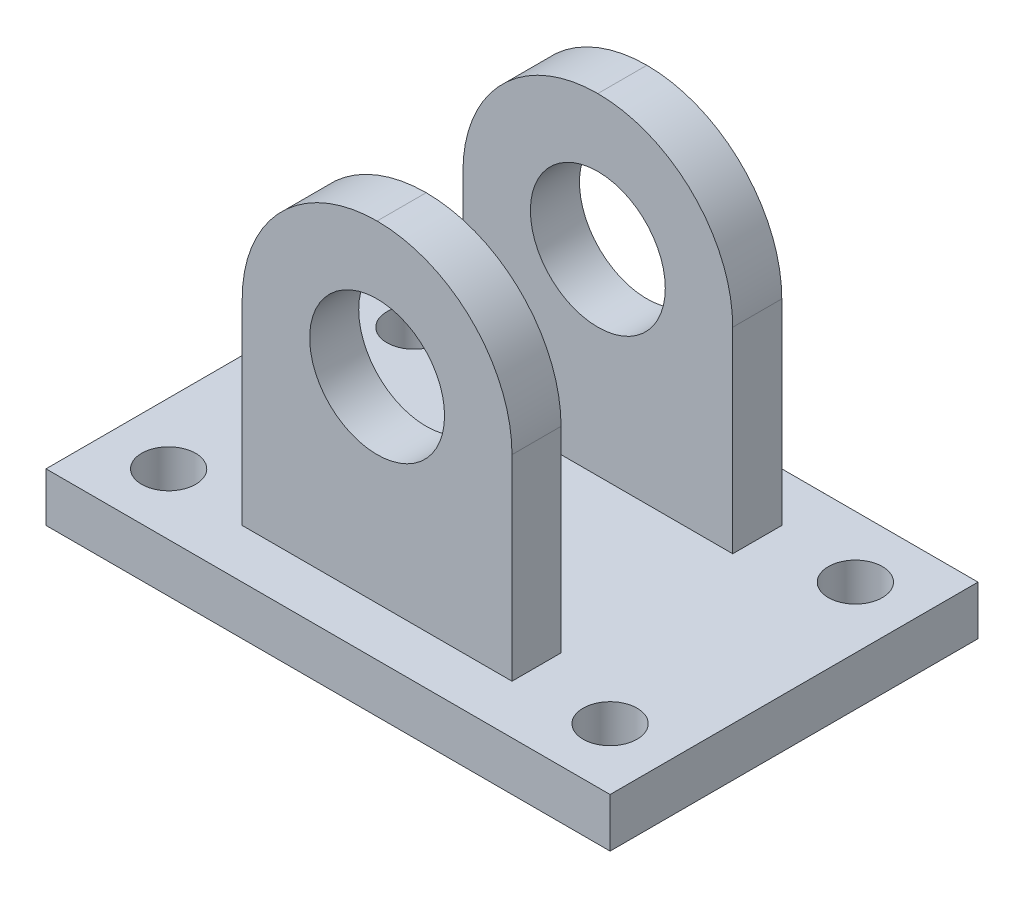
SolidWorks part; units mm, degrees
ref_plane "前视基准面" through (0, 0, 0) normal (0, 0, 1) x (1, 0, 0)
ref_plane "上视基准面" through (0, 0, 0) normal (0, 1, 0) x (1, 0, 0)
ref_plane "右视基准面" through (0, 0, 0) normal (1, 0, 0) x (0, 0, -1)
sketch "草图1" plane through (0, 0, 0) normal (0, 1, 0) x (1, 0, 0)
  line L1 (115, -75) -> (-115, -75)
  line L2 (115, -75) -> (115, 75)
  line L3 (115, 75) -> (-115, 75)
  line L4 (-115, -75) -> (-115, 75)
  line L5 (115, -75) -> (-115, 75) construction
  line L6 (115, 75) -> (-115, -75) construction
  point P0 (0, 0)
  dimension "D1" = 150
  dimension "D2" = 230
extrude "凸台-拉伸1" add sketch "草图1" along normal blind 20
sketch "草图2" plane through (0, 20, 0) normal (0, 1, 0) x (1, 0, 0)
  line L0 (-115, 0) -> (115, 0) construction
  line L1 (-55, 55) -> (55, 55)
  line L2 (-55, 55) -> (-55, 35)
  line L3 (-55, 35) -> (55, 35)
  line L4 (55, 55) -> (55, 35)
  line L5 (-115, 75) -> (-115, -75) construction
  line L6 (115, -75) -> (115, 75) construction
  point P10 (0, 35)
  dimension "D1" = 20
  dimension "D2" = 110
  dimension "D3" = 35
extrude "凸台-拉伸2" add sketch "草图2" along normal blind 135
mirror "镜向1" about plane through (0, 0, 0) normal (0, 0, 1) of "凸台-拉伸2"
fillet "圆角1" radius 55 4 edges at (-55, 155, -45) (55, 155, -45) (-55, 155, 45) (55, 155, 45)
sketch "草图4" plane through (0, 0, 55) normal (0, 0, 1) x (1, 0, 0)
  line L1 (-115, 0) -> (115, 0) construction
  circle A0 centre (0, 100) radius 27.5
  point P3 (0, 0)
  point P6 (0, 0)
  point P7 (-21.1115, 100)
  point P8 (0, 0)
  point P9 (0, 0)
  dimension "D1" = 55
  dimension "D2" = 100
extrude "切除-拉伸1" cut sketch "草图4" against normal through all
sketch "草图5" plane through (0, 20, 0) normal (0, 1, 0) x (1, 0, 0)
  line L0 (0, 75) -> (0, -75) construction
  line L1 (115, 75) -> (-115, 75) construction
  line L2 (-115, -75) -> (115, -75) construction
  line L3 (-115, 0) -> (115, 0) construction
  line L4 (-115, 75) -> (-115, -75) construction
  line L5 (115, -75) -> (115, 75) construction
  circle A0 centre (-90, 50) radius 11
  dimension "D1" = 180
  dimension "D3" = 22
  dimension "D2" = 100
extrude "切除-拉伸2" cut sketch "草图5" against normal through all
pattern_linear "阵列(线性)1" count 2 spacing 180 along (1, 0, 0) count 2 spacing 100 along (0, 0, 1) of "切除-拉伸2"
